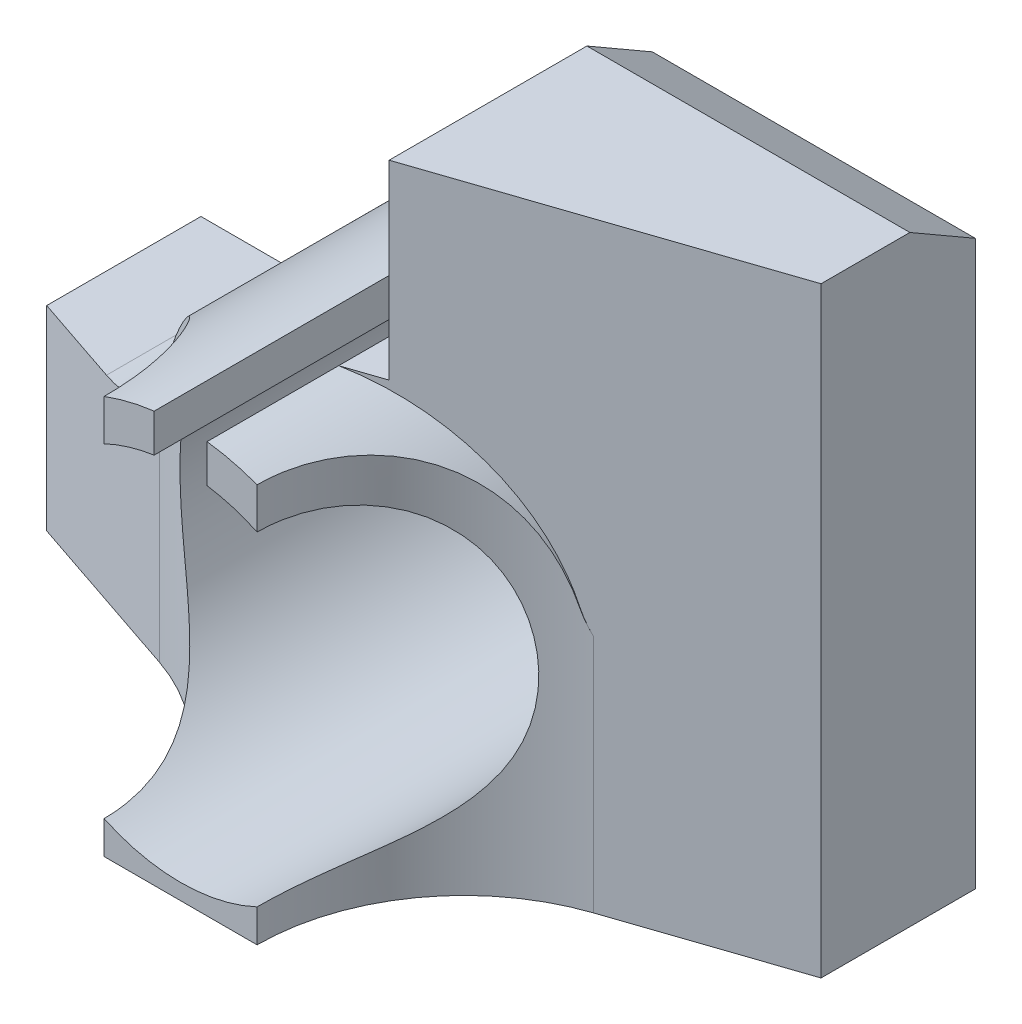
SolidWorks part; units mm, degrees
ref_plane "Front Plane" through (0, 0, 0) normal (0, 0, 1) x (1, 0, 0)
ref_plane "Top Plane" through (0, 0, 0) normal (0, 1, 0) x (1, 0, 0)
ref_plane "Right Plane" through (0, 0, 0) normal (1, 0, 0) x (0, 0, -1)
ref_plane "Plane1" through (0, -13.1255, 0) normal (0, 1, 0) x (1, 0, 0)
sketch "Sketch1" plane through (0, 0, 0) normal (0, 0, 1) x (1, 0, 0)
  line L0 (-14.605, 0) -> (-14.605, -13.1255)
  line L1 (15.5271, -13.1255) -> (-15.5271, -13.1255) construction
  line L2 (-14.605, -13.1255) -> (14.605, -13.1255)
  line L3 (14.605, -13.1255) -> (14.605, 0)
  circle A0 centre (0, 0) radius 12.065
  circle A2 centre (0, 0) radius 14.605
  dimension "D1" = 24.13
  dimension "D2" = 2.54
extrude "Boss-Extrude1" add sketch "Sketch1" against normal blind 27.4041 contours A2 L0 L2 | A2 L2 A0 | A2 L2 L3 region at (-12.3354, -10.0554, 0) region at (0, 14.2022, 0) region at (12.3354, -10.0554, 0)
sketch "Sketch2" plane through (0, 0, 0) normal (0, 1, 0) x (1, 0, 0)
  line L0 (-22.2367, 0) -> (22.2367, 0) construction
  line L1 (0, 0) -> (0, 50000) construction
  circle A0 centre (-19.05, 0) radius 13.9065
  circle A1 centre (19.05, 0) radius 13.9065
  dimension "D2" = 27.813
  dimension "D1" = 19.05
extrude "Cut-Extrude2" cut sketch "Sketch2" against normal mid plane 38.1
sketch "Sketch8" plane through (0, 0, 0) normal (0, 1, 0) x (1, 0, 0)
  line L0 (-5.1435, 0) -> (5.1435, 0) construction
  line L1 (-1.778, 27.4041) -> (1.778, 27.4041)
  line L2 (-1.778, 27.4041) -> (-1.778, 0)
  line L3 (-1.778, 0) -> (1.778, 0)
  line L4 (1.778, 27.4041) -> (1.778, 0)
  line L5 (14.605, 27.4041) -> (-14.605, 27.4041) construction
  point P6 (0, 0)
  dimension "D1" = 3.556
extrude "Cut-Extrude4" cut sketch "Sketch8" along normal through all
sketch "Sketch10" plane through (0, -13.1255, 0) normal (0, -1, 0) x (1, 0, 0)
  line L0 (-14.605, -13.177) -> (-26.035, -17.0327)
  line L1 (-26.035, -17.0327) -> (-26.035, -27.4041)
  line L2 (-26.035, -27.4041) -> (-14.605, -27.4041)
  line L3 (-14.605, -13.177) -> (-14.605, -27.4041)
  arc A0 (-14.605, -13.177) -> (-5.1435, 0) centre (-19.05, 0) ccw construction
  dimension "D1" = 11.43
extrude "Boss-Extrude6" add sketch "Sketch10" against normal blind 13.1267
mirror "Mirror3" about plane through (0, 0, 0) normal (1, 0, 0) of "Boss-Extrude6"
fillet "Fillet1" radius 6.35 2 edges at (-14.605, 0.0013, -20.2905) (14.605, 0.0013, -20.2905)
sketch "Sketch7" plane through (0, -13.1255, 0) normal (0, 1, 0) x (1, 0, 0)
  line L4 (-5.1435, 0) -> (5.1435, 0) construction
  circle A1 centre (-19.05, 21.336) radius 2.6543
  dimension "D1" = 5.3086
  dimension "D2" = 21.336
  dimension "D5" = 19.05
extrude "Cut-Extrude6" cut sketch "Sketch7" along normal blind 7.62
mirror "Mirror4" about plane through (0, 0, 0) normal (1, 0, 0) of "Cut-Extrude6"
sketch "Sketch11" plane through (0, 0, -27.4041) normal (0, 0, -1) x (-1, 0, 0)
  line L0 (-1.778, 14.4964) -> (-1.778, 11.9333) construction
  line L1 (-26.035, 0.0013) -> (-1.778, 0.0013)
  line L2 (-26.035, 0.0013) -> (-26.035, 27.305)
  line L3 (-26.035, 27.305) -> (-1.778, 27.305)
  line L4 (-1.778, 0.0013) -> (-1.778, 27.305)
  arc A0 (-1.778, 11.9333) -> (1.778, 11.9333) centre (0, 0) ccw construction
  arc A1 (-1.778, 11.9333) -> (1.778, 11.9333) centre (0, 0) ccw
  arc M5 (-1.778, 14.4964) -> (-13.918, 4.4266) centre (0, 0) ccw
  arc M6 (-13.918, 4.4266) -> (-19.9693, 0.0013) centre (-19.9693, 6.3513) cw
  line M7 (-19.9693, 0.0013) -> (-26.035, 0.0013)
  dimension "D1" = 27.3037
extrude "Boss-Extrude7" add sketch "Sketch11" against normal up to surface (14.4588 mm away) contours L4 L3 L2 M5 M7 M6 region at (15.7385, 15.8804, -27.4041) up to face at (18.5829, -3.4263, -14.5188)
sketch "Sketch12" plane through (1.778, 0, 0) normal (-1, 0, 0) x (0, 0, 1)
  line L0 (-8.85, 27.305) -> (-8.85, 14.4964) construction
  line L1 (-27.4041, 27.305) -> (-8.85, 27.305)
  line L2 (-27.4041, 27.305) -> (-27.4041, 14.4964)
  line L3 (-27.4041, 14.4964) -> (-8.85, 14.4964)
  line L4 (-8.85, 27.305) -> (-8.85, 14.4964)
  line L5 (-8.85, 14.4964) -> (0, 14.4964) construction
extrude "Cut-Extrude7" cut sketch "Sketch12" against normal blind 2.54
chamfer "Chamfer1" distance 2.54 angle 60 1 edges at (15.1765, 27.305, -27.4041) first distance on face at (-2.1671, 6.4114, -27.4041)
sketch "Sketch13" plane through (4.318, 0, 0) normal (-1, 0, 0) x (0, 0, 1)
  line L0 (-27.4041, 14.4964) -> (-9.7069, 14.4964) construction
  line L1 (-9.7069, 14.4964) -> (-9.7069, 27.305) construction
  circle A0 centre (-22.3561, 22.9546) radius 2.6543
  circle A1 centre (-16.6665, 17.2904) radius 2.6543
  point P4 (-13.6209, 18.4888)
  point P5 (-22.7877, 22.2885)
  point P6 (-15.6936, 17.9376)
  point P7 (-22.3402, 22.9585)
  point P8 (-16.6022, 17.842)
  point P9 (-16.6317, 17.4)
  dimension "D1" = 5.3086
  dimension "D2" = 2.794
  dimension "D3" = 5.6642
  dimension "D4" = 6.9596
  dimension "D5" = 5.6896
extrude "Cut-Extrude8" cut sketch "Sketch13" against normal blind 7.62
